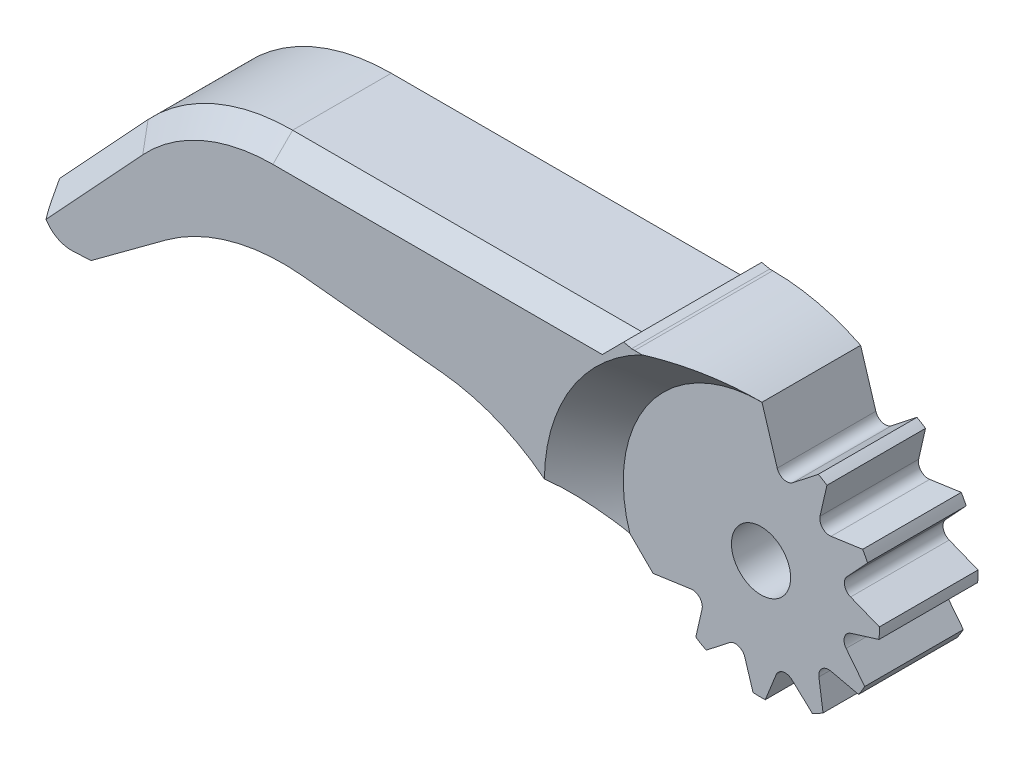
SolidWorks part; units mm, degrees
ref_plane "前视基准面" through (0, 0, 0) normal (0, 0, 1) x (1, 0, 0)
ref_plane "上视基准面" through (0, 0, 0) normal (0, 1, 0) x (1, 0, 0)
ref_plane "右视基准面" through (0, 0, 0) normal (1, 0, 0) x (0, 0, -1)
sketch "Sketch1" plane through (0, 0, 0) normal (1, 0, 0) x (0, 0, -1)
  line L1 (-14.76, 15.6242) -> (2.04, 15.6242)
  line L2 (-14.76, 15.6242) -> (-14.76, -2.5758)
  line L3 (-14.76, -2.5758) -> (2.04, -2.5758)
  line L4 (2.04, 15.6242) -> (2.04, -2.5758)
  line L5 (-14.76, 15.6242) -> (2.04, -2.5758) construction
  line L6 (-14.76, -2.5758) -> (2.04, 15.6242) construction
  point P0 (-6.36, 6.5242)
  dimension "D1" = 16.8
  dimension "D2" = 18.2
extrude "Boss-Extrude1" add sketch "Sketch1" along normal blind 7.91
sketch "Sketch2" plane through (7.91, 0, 0) normal (1, 0, 0) x (0, 0, -1)
  line L0 (2.04, -2.5758) -> (2.04, 15.6242) construction
  line L1 (-9.47, 19.1945) -> (-8.47, 19.1945)
  line L2 (-9.47, 19.1945) -> (-9.47, -5.8055)
  line L3 (-9.47, -5.8055) -> (-8.47, -5.8055)
  line L4 (-8.47, 19.1945) -> (-8.47, -5.8055)
  dimension "D1" = 10.51
  dimension "D2" = 1
  dimension "D3" = 25
extrude "Boss-Extrude2" add sketch "Sketch2" against normal up to surface (7.91 mm away) contours L1 L4 L3 L2 up to face at (0, 6.5242, 6.36)
sketch "Sketch3" plane through (0, 0, 9.47) normal (0, 0, 1) x (1, 0, 0)
  line L0 (0, 15.6242) -> (0, -2.5758) construction
  line L1 (-3.955, -4.4308) -> (3.955, -4.4308) construction
  line L2 (-3.955, -4.4308) -> (-3.955, 17.4792) construction
  line L3 (-3.955, 17.4792) -> (3.955, 17.4792) construction
  line L4 (3.955, -4.4308) -> (3.955, 17.4792) construction
  line L5 (-3.955, -4.4308) -> (3.955, 17.4792) construction
  line L6 (-3.955, 17.4792) -> (3.955, -4.4308) construction
  circle A0 centre (3.955, 17.4792) radius 1
  circle A1 centre (3.955, -4.4308) radius 1
  point P0 (0, 6.5242)
  dimension "D1" = 21.91
extrude "Cut-Extrude1" cut sketch "Sketch3" against normal blind 21.9
sketch "Sketch4" plane through (0, 0, 14.76) normal (0, 0, 1) x (1, 0, 0)
  circle A0 centre (3.955, 11.3332) radius 1.9516
extrude "Boss-Extrude3" add sketch "Sketch4" along normal blind 3
sketch "Sketch5" plane through (0, 0, 17.76) normal (0, 0, 1) x (1, 0, 0)
  line L0 (3.955, 5.1286) -> (-1.9792, 5.1286) construction
  line L1 (-28.0129, 9.5262) -> (-30.248, 9.4243)
  line L2 (-30.6067, 11.3332) -> (-30.248, 9.4243)
  line L4 (-28.0129, 9.5262) -> (-21.1255, 14.6069)
  line L10 (-23.1541, 19.3636) -> (-30.6067, 11.3332)
  line L11 (-21.1255, 14.6069) -> (-6.6651, 13.1507)
  line L12 (-6.6651, 13.1507) -> (-0.6973, 7.228)
  line L13 (-23.1541, 19.3636) -> (2.0257, 19.3636)
  line L14 (2.0257, 19.3636) -> (6.545, 16.9714)
  circle A0 centre (3.955, 11.3332) radius 1.5
  circle A1 centre (3.955, 11.3332) radius 6.2046 construction
  arc A2 (-0.6973, 7.228) -> (6.545, 16.9714) centre (3.955, 11.3332) ccw
  dimension "D1" = 12.4092
  dimension "D2" = 3
extrude "Boss-Extrude4" add sketch "Sketch5" along normal blind 7 separate body
sketch "Sketch6" plane through (0, 0, 0) normal (-1, 0, 0) x (0, 0, 1)
  line L0 (17.76, 22.7282) -> (-5.1444, 21.9553)
  line L1 (-5.1444, 21.9553) -> (-2.936, -7.1287)
  line L2 (-2.936, -7.1287) -> (17.0897, -7.5405)
  line L3 (17.0897, -7.5405) -> (17.76, 5.9646)
  line L4 (17.76, 5.9646) -> (17.76, 22.7282)
extrude "Cut-Extrude2" cut sketch "Sketch6" against normal through all both and the other way through all
sketch "Sketch7" plane through (0, 0, 24.76) normal (0, 0, 1) x (1, 0, 0)
  line L0 (4.9903, 7.3855) -> (3.7934, 4.3982)
  line L43 (3.955, 11.3332) -> (3.955, 22.9571) construction
  line L45 (3.7934, 4.3982) -> (7.2192, 5.3161)
  line L46 (7.2192, 5.3161) -> (4.9903, 7.3855)
  line L47 (2.9197, 7.3855) -> (0.3896, 5.3968)
  line L48 (0.3896, 5.3968) -> (3.8153, 4.4789)
  line L49 (3.8153, 4.4789) -> (2.9197, 7.3855)
  line L50 (1.1266, 8.4208) -> (-2.059, 7.9636)
  line L51 (-2.059, 7.9636) -> (0.4488, 5.4558)
  line L52 (0.4488, 5.4558) -> (1.1266, 8.4208)
  line L53 (0.0913, 10.2139) -> (-2.8961, 11.4108)
  line L54 (-2.8961, 11.4108) -> (-1.9781, 7.985)
  line L55 (-1.9781, 7.985) -> (0.0913, 10.2139)
  line L56 (0.0913, 12.2845) -> (-1.8974, 14.8146)
  line L57 (-1.8974, 14.8146) -> (-2.8153, 11.3889)
  line L58 (-2.8153, 11.3889) -> (0.0913, 12.2845)
  line L59 (1.1266, 14.0776) -> (0.6694, 17.2632)
  line L60 (0.6694, 17.2632) -> (-1.8384, 14.7554)
  line L61 (-1.8384, 14.7554) -> (1.1266, 14.0776)
  line L62 (2.9197, 15.1129) -> (4.1166, 18.1003)
  line L63 (4.1166, 18.1003) -> (0.6908, 17.1823)
  line L64 (0.6908, 17.1823) -> (2.9197, 15.1129)
  line L65 (4.9903, 15.1129) -> (7.5204, 17.1016)
  line L66 (7.5204, 17.1016) -> (4.0947, 18.0195)
  line L67 (4.0947, 18.0195) -> (4.9903, 15.1129)
  line L68 (6.7834, 14.0776) -> (9.969, 14.5348)
  line L69 (9.969, 14.5348) -> (7.4612, 17.0426)
  line L70 (7.4612, 17.0426) -> (6.7834, 14.0776)
  line L71 (7.8187, 12.2845) -> (10.8061, 11.0877)
  line L72 (10.8061, 11.0877) -> (9.8881, 14.5134)
  line L73 (9.8881, 14.5134) -> (7.8187, 12.2845)
  line L74 (7.8187, 10.2139) -> (9.8074, 7.6838)
  line L75 (9.8074, 7.6838) -> (10.7253, 11.1095)
  line L76 (10.7253, 11.1095) -> (7.8187, 10.2139)
  line L77 (6.7834, 8.4208) -> (7.2406, 5.2352)
  line L78 (7.2406, 5.2352) -> (9.7484, 7.7431)
  line L79 (9.7484, 7.7431) -> (6.7834, 8.4208)
  line L80 (3.955, 11.2492) -> (4.9903, 7.3855) construction
  dimension "D1" = 4
  dimension "D2" = 12
extrude "Cut-Extrude4" cut sketch "Sketch7" against normal through all both and the other way through all
sketch "Sketch8" plane through (0, 0, 24.76) normal (0, 0, 1) x (1, 0, 0)
  line L0 (-3.5021, 10.0116) -> (-2.2193, 8.7384)
  line L1 (-6.6651, 13.1507) -> (-2.1658, 8.6853) construction
  line L3 (0.1979, 10.3812) -> (1.3389, 13.6065)
  line L4 (1.3389, 13.6065) -> (4.5622, 15.1451)
  line L8 (-1.0107, 19.4519) -> (-5.403, 15.0263)
  line L9 (-5.403, 15.0263) -> (-3.5021, 10.0116)
  line L10 (-2.2193, 8.7384) -> (-1.5169, 8.0414)
  line L11 (-1.5169, 8.0414) -> (0.1979, 10.0116)
  line L12 (0.1979, 10.0116) -> (0.1979, 10.3812)
  line L13 (4.5622, 15.1451) -> (4.1863, 17.7224)
  line L14 (4.0947, 18.0195) -> (4.9903, 15.1129) construction
  line L15 (4.1863, 17.7224) -> (3.9866, 18.3704)
  line L16 (3.9866, 18.3704) -> (-1.0107, 19.4519)
extrude "Boss-Extrude5" add sketch "Sketch8" against normal up to surface (7 mm away) up to face at (2.5757, 16.7985, 17.76)
sketch "Sketch9" plane through (0, 0, 24.76) normal (0, 0, 1) x (1, 0, 0)
  line L0 (5.9128, 17.0048) -> (7.7508, 18.7514)
  line L1 (7.7508, 18.7514) -> (14.7411, 11.8142)
  line L2 (14.7411, 11.8142) -> (2.6078, 0.7055)
  line L3 (2.6078, 0.7055) -> (-4.9657, 1.9261)
  line L4 (-4.9657, 1.9261) -> (-6.9353, 6.5312)
  line L5 (-6.9353, 6.5312) -> (-0.7964, 7.6693)
  circle A0 centre (3.955, 11.3332) radius 6 construction
  arc A1 (-0.7964, 7.6693) -> (5.9128, 17.0048) centre (3.955, 11.3332) ccw
  dimension "D1" = 6
extrude "Cut-Extrude5" cut sketch "Sketch9" against normal through all both and the other way through all
fillet "Fillet1" radius 0.5 8 edges at (4.9903, 15.1129, 21.26) (6.7834, 14.0776, 21.26) (7.8187, 12.2845, 21.26) (7.8187, 10.2139, 21.26) (6.7834, 8.4208, 21.26) (1.1266, 8.4208, 21.26) (2.9197, 7.3855, 21.26) (4.9903, 7.3855, 21.26)
fillet "Fillet2" radius 0.8 rebuild error yes
sketch "Sketch10" plane through (0, 0, 24.76) normal (0, 0, 1) x (1, 0, 0)
  line L0 (4.1549, 17.8241) -> (4.0031, 18.3169)
  line L1 (4.0947, 18.0195) -> (4.7759, 15.8087) construction
  line L2 (4.0031, 18.3169) -> (3.8435, 18.4014)
  line L3 (3.8435, 18.4014) -> (4.3437, 18.9604)
  line L4 (4.3437, 18.9604) -> (5.7702, 18.2053)
  line L5 (5.7702, 18.2053) -> (5.3786, 17.3971)
  line L6 (5.3786, 17.3971) -> (4.1549, 17.8241)
extrude "Cut-Extrude6" cut sketch "Sketch10" against normal through all both and the other way through all
fillet "Fillet3" radius 10 4 edges at (2.0257, 19.3636, 21.26) (-23.1541, 19.3636, 21.26) (-6.6651, 13.1507, 21.26) (-21.1255, 14.6069, 21.26)
fillet "Fillet4" radius 1.5 1 edges at (-30.248, 9.4243, 21.26)
chamfer "Chamfer1" distance 1 angle 45 6 edges at (-28.3641, 13.7496, 17.76) (-22.7902, 18.5294, 17.76) (-9.945, 19.3636, 17.76) (-28.3641, 13.7496, 24.76) (-22.7902, 18.5294, 24.76) (-9.945, 19.3636, 24.76)
sketch "Sketch11" plane through (0, 0, 24.76) normal (0, 0, 1) x (1, 0, 0)
  circle A0 centre (3.955, 11.3332) radius 3.5028
extrude "Cut-Extrude7" cut sketch "Sketch11" against normal blind 1
sketch "Sketch12" plane through (0, 0, 24.76) normal (0, 0, 1) x (1, 0, 0)
  circle A0 centre (3.955, 11.3332) radius 6.9839
extrude "Cut-Extrude8" cut sketch "Sketch12" against normal blind 2
chamfer "Chamfer2" distance 2 angle 45 1 edges at (-1.6683, 15.4748, 24.76)
equation "\"16。8\"=83.7992"
